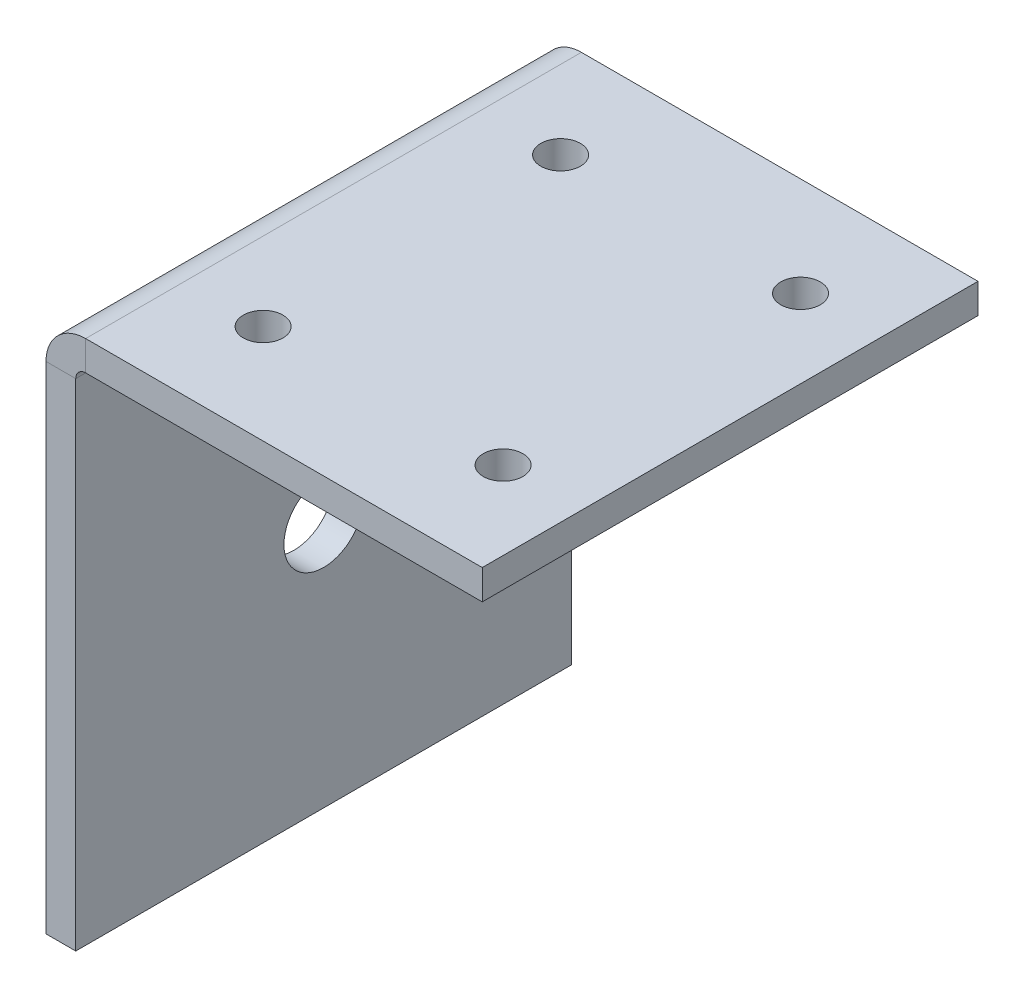
SolidWorks part; units mm, degrees
note: The reader was unsure of these and kept them because the rebuilt part matched: flange length of "边线-法兰1".
ref_plane "前视基准面" through (0, 0, 0) normal (0, 0, 1) x (1, 0, 0)
ref_plane "上视基准面" through (0, 0, 0) normal (0, 1, 0) x (1, 0, 0)
ref_plane "右视基准面" through (0, 0, 0) normal (1, 0, 0) x (0, 0, -1)
sketch "草图1" plane through (0, 0, 0) normal (0, 1, 0) x (1, 0, 0)
  line L1 (-20, -25) -> (20, -25)
  line L2 (-20, -25) -> (-20, 25)
  line L3 (-20, 25) -> (20, 25)
  line L4 (20, -25) -> (20, 25)
  circle A0 centre (12.1, 15) radius 2
  circle A1 centre (-12.1, -15) radius 2
  circle A2 centre (-12.1, 15) radius 2
  circle A3 centre (12.1, -15) radius 2
base flange "基体-法兰1" sketch "草图1" thickness 3 reverse thickness direction no parameters "D1"=0.762
edge flange "边线-法兰1" sketch "草图11" flange angle 90 flange length 54 flange position bend outside bend radius 1 thickness 3 relief rectangular parameters "D6"=10
bend "边线折弯1" bend radius 1 bend angle 90 parameters "D5"=1
sketch "草图11" plane through (-20, -3, 0) normal (-1, 0, 0) x (0, 0, -1)
  line L0 (25, 0) -> (-25, 0) construction
  line L1 (25, 0) -> (-25, 0)
  line L2 (-25, 0) -> (-25, 51)
  line L3 (-25, 51) -> (25, 51)
  line L4 (25, 51) -> (25, 0)
sketch "草图12" plane through (-24, 0, 0) normal (-1, 0, 0) x (0, 0, 1)
  line L0 (-25, -4) -> (25, -4) construction
  circle A0 centre (0, -29) radius 4
  dimension "D1" = 25
extrude "切除-拉伸1" cut sketch "草图12" against normal through all normal cut yes
sketch "折弯-线1" plane through (0, 0, 0) normal (0, 1, 0) x (1, 0, 0)
sketch "边界框1" plane through (0, 0, 0) normal (0, 1, 0) x (1, 0, 0)
sheet metal parameters "钣金6" thickness 3 parameters "D1"=0.762
flat pattern "平板型式6" [suppressed]
sketch "折弯-线2" plane through (0, 0, 0) normal (0, 1, 0) x (1, 0, 0)
sketch "边界框2" [suppressed] plane through (0, 0, 0) normal (0, 1, 0) x (1, 0, 0)
sheet metal parameters "钣金7" thickness 3 parameters "D1"=0.762
flat pattern "平板型式6" [suppressed]
sketch "折弯-线2" plane through (0, 0, 0) normal (0, 1, 0) x (1, 0, 0)
sketch "边界框2" [suppressed] plane through (0, 0, 0) normal (0, 1, 0) x (1, 0, 0)
bend of the flat pattern "展开-<边线折弯1>1"
sheet metal parameters "钣金9" thickness 3 parameters "D1"=0.762
flat pattern "平板型式6" [suppressed]
sketch "折弯-线2" plane through (0, 0, 0) normal (0, 1, 0) x (1, 0, 0)
sketch "边界框2" [suppressed] plane through (0, 0, 0) normal (0, 1, 0) x (1, 0, 0)
bend of the flat pattern "展开-<边线折弯1>1"
